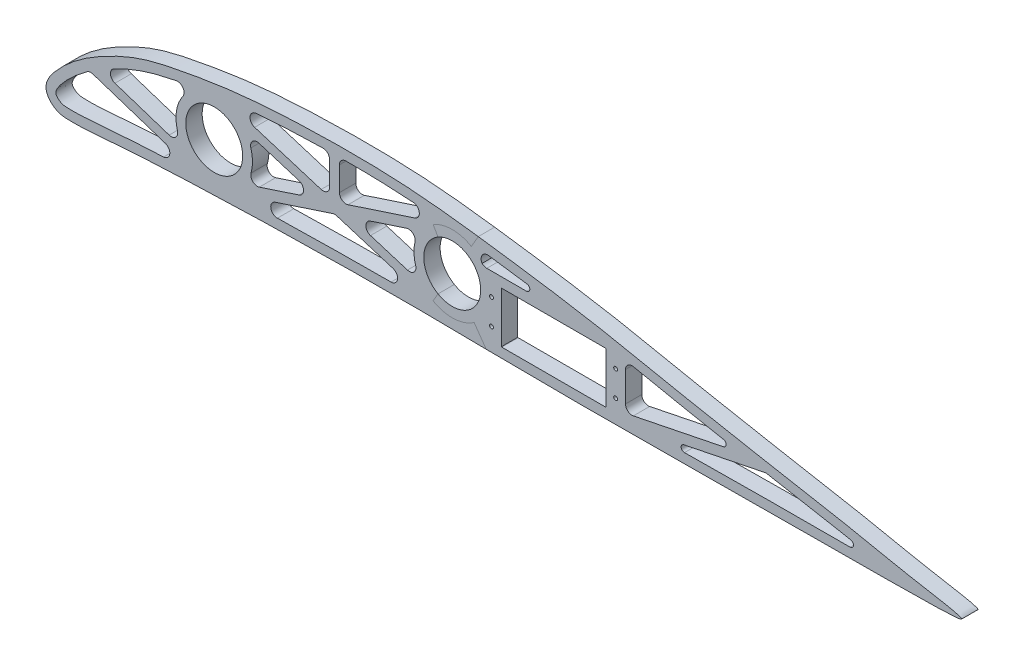
SolidWorks part; units mm, degrees
ref_plane "Front Plane" through (0, 0, 0) normal (0, 0, 1) x (1, 0, 0)
ref_plane "Top Plane" through (0, 0, 0) normal (0, 1, 0) x (1, 0, 0)
ref_plane "Right Plane" through (0, 0, 0) normal (1, 0, 0) x (0, 0, -1)
curve "Curve2"
  spline degree 3 poles (335.2351, -1.0002, 0) (365.8399, -0.7578, 0) (335.068, 4.1779, 0) (315.5959, 8.5123, 0) (283.7557, 14.215, 0) (248.7119, 20.6229, 0) (213.0993, 28.2961, 0) (177.4389, 33.5333, 0) (141.8604, 38.2675, 0) (106.138, 38.4812, 0) (76.3937, 36.9037, 0) (52.7831, 32.9871, 0) (37.7504, 29.8496, 0) (26.1237, 24.7709, 0) (17.1735, 19.9778, 0) (9.6748, 14.5696, 0) (3.4982, 8.4999, 0) (-2.4515, 0.9243, 0) (3.7121, -5.3477, 0) (10.4481, -5.6922, 0) (17.8596, -5.3149, 0) (26.7315, -4.5493, 0) (38.5676, -3.7193, 0) (53.3791, -3.044, 0) (77.0722, -2.1352, 0) (106.6998, -1.4625, 0) (142.26, -1.14, 0) (177.831, -1.7864, 0) (213.3484, -1.8913, 0) (249.0801, -1.7216, 0) (283.9883, -1.2505, 0) (315.6348, -1.3975, 0) (335.2351, -1.0002, 0) (365.8399, -0.7578, 0) (335.068, 4.1779, 0) knots -0.097522 -0.048769 -0.024396 0 0.025026 0.049952 0.099684 0.149416 0.199259 0.248703 0.297849 0.346623 0.395439 0.420071 0.445104 0.458263 0.47205 0.487006 0.495455 0.509299 0.518413 0.524589 0.536779 0.54899 0.561193 0.585585 0.609963 0.658715 0.707463 0.756228 0.804981 0.853734 0.902478 0.951231 0.975604 1 1.025026 1.049952 1.099684 periodic
sketch "Sketch3" plane through (0, 0, 0) normal (0, 0, 1) x (1, 0, 0)
  line L1 (324.6822, 2.6136) -> (325.3535, 2.6233)
  line L2 (325.3535, 2.6233) -> (307.9141, 5.9353)
  spline S0 degree 3 poles (335.2351, -1.0002) (365.8399, -0.7578) (335.068, 4.1779) (315.5959, 8.5123) (283.7557, 14.215) (248.7119, 20.6229) (213.0993, 28.2961) (177.4389, 33.5333) (141.8604, 38.2675) (106.138, 38.4812) (76.3937, 36.9037) (52.7831, 32.9871) (37.7504, 29.8496) (26.1237, 24.7709) (17.1735, 19.9778) (9.6748, 14.5696) (3.4982, 8.4999) (-2.4515, 0.9243) (3.7121, -5.3477) (10.4481, -5.6922) (17.8596, -5.3149) (26.7315, -4.5493) (38.5676, -3.7193) (53.3791, -3.044) (77.0722, -2.1352) (106.6998, -1.4625) (142.26, -1.14) (177.831, -1.7864) (213.3484, -1.8913) (249.0801, -1.7216) (283.9883, -1.2505) (315.6348, -1.3975) (335.2351, -1.0002) (365.8399, -0.7578) (335.068, 4.1779) knots -0.097522 -0.048769 -0.024396 0 0.025026 0.049952 0.099684 0.149416 0.199259 0.248703 0.297849 0.346623 0.395439 0.420071 0.445104 0.458263 0.47205 0.487006 0.495455 0.509299 0.518413 0.524589 0.536779 0.54899 0.561193 0.585585 0.609963 0.658715 0.707463 0.756228 0.804981 0.853734 0.902478 0.951231 0.975604 1 1.025026 1.049952 1.099684 only from (355.6, 0) to (355.6, 0) construction
  spline S3 degree 3 poles (307.9141, 5.9353) (307.0863, 6.0925) (305.4377, 6.4038) (302.0805, 7.0309) (296.1287, 8.128) (287.4713, 9.6948) (277.2294, 11.5453) (267.2024, 13.3828) (257.2748, 15.2495) (244.0596, 17.8287) (227.4526, 21.2972) (207.5658, 25.126) (187.5939, 28.193) (167.4715, 31.0351) (147.4425, 33.4718) (127.4415, 34.5599) (107.2387, 34.4562) (90.4094, 33.8122) (77.0776, 32.6931) (67.1623, 31.4738) (57.2616, 29.8392) (47.317, 27.9873) (39.4207, 26.0026) (33.4304, 23.7904) (28.9582, 21.7979) (24.5546, 19.6052) (20.3228, 17.2265) (16.904, 15.0105) (14.2974, 13.1153) (12.4283, 11.6418) (10.6708, 10.1297) (9.0191, 8.5675) (7.3511, 6.8261) (5.6256, 4.8715) (4.5188, 3.3123) (3.9691, 2.2408) (3.7413, 1.5904) (3.6763, 1.1383) (3.6939, 0.9054) (3.7663, 0.6498) (4.0404, 0.1533) (4.499, -0.3861) (5.086, -0.8863) (5.7247, -1.2682) (6.2758, -1.482) (7.0038, -1.6418) (8.2328, -1.7573) (10.2939, -1.7757) (12.7019, -1.7335) (15.1576, -1.6209) (17.6379, -1.463) (20.9776, -1.2167) (25.1904, -0.8679) (32.0053, -0.347) (40.5143, 0.1734) (50.7079, 0.6434) (60.875, 1.0577) (71.055, 1.4259) (84.63, 1.835) (101.5966, 2.2078) (121.9512, 2.4949) (142.338, 2.5619) (162.7122, 2.3066) (183.0031, 2.0331) (203.2832, 1.9499) (223.6381, 1.9709) (243.9997, 2.078) (260.7266, 2.2598) (274.2438, 2.3928) (284.5572, 2.4608) (295.1146, 2.4761) (303.8218, 2.4778) (310.5638, 2.492) (315.4692, 2.5141) (320.164, 2.5522) (323.1654, 2.5918) (324.6822, 2.6136) knots 0.06655 0.06655 0.06655 0.06655 0.070034 0.073518 0.080485 0.09442 0.108355 0.122289 0.136224 0.150159 0.178028 0.205897 0.233767 0.261636 0.289506 0.317375 0.345244 0.373114 0.387048 0.400983 0.414918 0.428853 0.442787 0.449755 0.456722 0.463689 0.470657 0.477624 0.481108 0.484591 0.488075 0.491559 0.495042 0.498526 0.50201 0.503752 0.505493 0.507235 0.508977 0.510719 0.512461 0.514203 0.515944 0.517686 0.519428 0.52117 0.522912 0.526395 0.529879 0.533363 0.536846 0.54033 0.547298 0.554265 0.5682 0.582134 0.596069 0.610004 0.623938 0.651808 0.679677 0.707547 0.735416 0.763285 0.791155 0.819024 0.846894 0.874763 0.888698 0.902632 0.916567 0.930502 0.937469 0.944436 0.951404 0.958371 0.958371 0.958371 0.958371
  spline S4 degree 3 poles (335.2351, -1.0002) (365.8399, -0.7578) (335.068, 4.1779) (315.5959, 8.5123) (283.7557, 14.215) (248.7119, 20.6229) (213.0993, 28.2961) (177.4389, 33.5333) (141.8604, 38.2675) (106.138, 38.4812) (76.3937, 36.9037) (52.7831, 32.9871) (37.7504, 29.8496) (26.1237, 24.7709) (17.1735, 19.9778) (9.6748, 14.5696) (3.4982, 8.4999) (-2.4515, 0.9243) (3.7121, -5.3477) (10.4481, -5.6922) (17.8596, -5.3149) (26.7315, -4.5493) (38.5676, -3.7193) (53.3791, -3.044) (77.0722, -2.1352) (106.6998, -1.4625) (142.26, -1.14) (177.831, -1.7864) (213.3484, -1.8913) (249.0801, -1.7216) (283.9883, -1.2505) (315.6348, -1.3975) (335.2351, -1.0002) (365.8399, -0.7578) (335.068, 4.1779) knots -0.097522 -0.048769 -0.024396 0 0.025026 0.049952 0.099684 0.149416 0.199259 0.248703 0.297849 0.346623 0.395439 0.420071 0.445104 0.458263 0.47205 0.487006 0.495455 0.509299 0.518413 0.524589 0.536779 0.54899 0.561193 0.585585 0.609963 0.658715 0.707463 0.756228 0.804981 0.853734 0.902478 0.951231 0.975604 1 1.025026 1.049952 1.099684 only from (355.6, 0) to (355.6, 0)
extrude "Outline" add sketch "Sketch3" along normal blind 6.35
curve "Curve3"
  spline degree 3 poles (355.6, 0, 0) (349.661, 1.3249, 0) (337.8068, 3.9693, 0) (314.0213, 8.6322, 0) (284.2903, 14.1743, 0) (248.5683, 20.6338, 0) (213.1375, 28.2932, 0) (177.4288, 33.5341, 0) (141.8629, 38.2672, 0) (106.1377, 38.4813, 0) (76.3924, 36.9036, 0) (52.7856, 32.9873, 0) (37.7426, 29.8491, 0) (26.1384, 24.7718, 0) (17.1124, 19.9739, 0) (9.8782, 14.5828, 0) (2.9933, 8.4673, 0) (1.1467, 3.2437, 0) (0, 0, 0) knots 0 0 0 0 0.049139 0.09808 0.195728 0.293375 0.391241 0.488324 0.584822 0.680589 0.776437 0.824803 0.873954 0.899793 0.926862 0.956228 0.972818 1 1 1 1
curve "Curve4"
  spline degree 3 poles (0, 0, 0) (1.2949, -2.0031, 0) (3.4671, -5.3636, 0) (10.5655, -5.6846, 0) (17.8199, -5.3174, 0) (26.7419, -4.5486, 0) (38.5617, -3.7197, 0) (53.3811, -3.0439, 0) (77.0712, -2.1353, 0) (106.6995, -1.4625, 0) (142.2626, -1.1402, 0) (177.8212, -1.7857, 0) (213.3851, -1.8941, 0) (248.9429, -1.7111, 0) (284.5004, -1.2895, 0) (314.1274, -1.2827, 0) (337.8466, -1.1991, 0) (349.6804, -0.3998, 0) (355.6, 0, 0) knots 0 0 0 0 0.018575 0.03116 0.056003 0.080886 0.105755 0.155463 0.205144 0.304495 0.40384 0.503218 0.602571 0.701924 0.80126 0.900613 0.950284 1 1 1 1
sketch "Sketch4" plane through (0, 0, 6.35) normal (0, 0, 1) x (1, 0, 0)
  line L0 (157.6922, 2.3692) -> (157.6922, 0.8557)
  line L1 (176.7422, 2.1257) -> (217.3822, 2.1257)
  line L2 (176.7422, 2.1257) -> (176.7422, 21.9377)
  line L3 (176.7422, 21.9377) -> (217.3822, 21.9377)
  line L4 (217.3822, 2.1257) -> (217.3822, 21.9377)
  line L5 (165.9635, 0.8557) -> (225.0022, 0.8557)
  line L7 (169.8663, 25.7477) -> (213.3765, 25.7477)
  line L8 (225.0022, 0.8557) -> (225.0022, 22.8309)
  line L9 (157.6922, 0.8557) -> (165.9635, 0.8557)
  line L12 (213.3765, 25.7477) -> (225.0022, 22.8309)
  circle A0 centre (65.2362, 16.0821) radius 11.049
  circle A1 centre (65.2362, 16.0821) radius 14.859
  circle A2 centre (157.6922, 17.2282) radius 11.049
  arc A3 (169.8663, 25.7477) -> (157.6922, 2.3692) centre (157.6922, 17.2282) ccw
  spline S0 degree 3 poles (-1038.5734, -1708.4775) (56.5957, 197.5041) (-23.9133, -4.1254) (10.5655, -5.6846) (17.8199, -5.3174) (26.7419, -4.5486) (38.5617, -3.7197) (53.3811, -3.0439) (77.0712, -2.1353) (106.6995, -1.4625) (142.2626, -1.1402) (177.8212, -1.7857) (213.3851, -1.8941) (248.9429, -1.7111) (284.5004, -1.2895) (314.1274, -1.2827) (467.1025, -0.7435) (604.2683, 106.9608) (814.6729, -1933.1464) knots -0.216018 -0.216018 -0.216018 -0.216018 0.018575 0.03116 0.056003 0.080886 0.105755 0.155463 0.205144 0.304495 0.40384 0.503218 0.602571 0.701924 0.80126 0.900613 0.950284 2.083015 2.083015 2.083015 2.083015 only from (0, 0) to (355.6, 0) construction
  spline S1 degree 3 poles (0, 0) (1.2949, -2.0031) (3.4671, -5.3636) (10.5655, -5.6846) (17.8199, -5.3174) (26.7419, -4.5486) (38.5617, -3.7197) (53.3811, -3.0439) (77.0712, -2.1353) (106.6995, -1.4625) (142.2626, -1.1402) (177.8212, -1.7857) (213.3851, -1.8941) (248.9429, -1.7111) (284.5004, -1.2895) (314.1274, -1.2827) (337.8466, -1.1991) (349.6804, -0.3998) (355.6, 0) knots 0 0 0 0 0.018575 0.03116 0.056003 0.080886 0.105755 0.155463 0.205144 0.304495 0.40384 0.503218 0.602571 0.701924 0.80126 0.900613 0.950284 1 1 1 1 construction
  spline S2 degree 3 poles (1264.4447, 1754.3849) (679.5845, -139.9452) (510.5114, -29.8876) (314.0213, 8.6322) (284.2903, 14.1743) (248.5683, 20.6338) (213.1375, 28.2932) (177.4288, 33.5341) (141.8629, 38.2672) (106.1377, 38.4813) (76.3924, 36.9036) (52.7856, 32.9873) (37.7426, 29.8491) (26.1384, 24.7718) (17.1124, 19.9739) (9.8782, 14.5828) (-28.7294, -19.7107) (107.4887, -169.8565) (-1713.5684, 1028.2618) knots -1.421165 -1.421165 -1.421165 -1.421165 0.049139 0.09808 0.195728 0.293375 0.391241 0.488324 0.584822 0.680589 0.776437 0.824803 0.873954 0.899793 0.926862 0.956228 0.972818 1.336994 1.336994 1.336994 1.336994 only from (355.6, 0) to (0, 0) construction
  spline S3 degree 3 poles (355.6, 0) (349.661, 1.3249) (337.8068, 3.9693) (314.0213, 8.6322) (284.2903, 14.1743) (248.5683, 20.6338) (213.1375, 28.2932) (177.4288, 33.5341) (141.8629, 38.2672) (106.1377, 38.4813) (76.3924, 36.9036) (52.7856, 32.9873) (37.7426, 29.8491) (26.1384, 24.7718) (17.1124, 19.9739) (9.8782, 14.5828) (2.9933, 8.4673) (1.1467, 3.2437) (0, 0) knots 0 0 0 0 0.049139 0.09808 0.195728 0.293375 0.391241 0.488324 0.584822 0.680589 0.776437 0.824803 0.873954 0.899793 0.926862 0.956228 0.972818 1 1 1 1 construction
  spline S4 degree 1 poles (3.1997, 2.0683) (355.3433, 3.8013) knots 0 0 1 1 construction
  spline S5 degree 3 poles (3.1997, 2.0683) (3.3321, 1.8636) (3.6027, 1.445) (4.1055, 0.6857) (4.9359, -0.4817) (5.6225, -1.1441) (6.009, -1.3731) (6.2112, -1.4673) (6.7384, -1.6184) (7.7394, -1.7276) (9.0432, -1.7604) (10.4239, -1.7667) (12.2132, -1.743) (14.4421, -1.6605) (17.1268, -1.4991) (19.8677, -1.2997) (22.6408, -1.0794) (26.3762, -0.7752) (31.0669, -0.4219) (36.6781, -0.0599) (44.1669, 0.3502) (52.9307, 0.7361) (61.6818, 1.0858) (69.1483, 1.3554) (77.1939, 1.6165) (90.8411, 1.9875) (109.5082, 2.3415) (131.3685, 2.5726) (148.9932, 2.4807) (160.7191, 2.3302) (167.1321, 2.2447) (173.5416, 2.1604) (184.1772, 2.0407) (200.6606, 1.9512) (221.4021, 1.963) (243.7529, 2.0787) (266.1087, 2.3057) (284.771, 2.4686) (299.6966, 2.5154) (310.8807, 2.5367) (322.0754, 2.554) (333.2026, 2.6081) (344.2003, 3.0428) (351.6389, 3.5511) (355.3433, 3.8013) knots 0 0 0 0 0.001953 0.003906 0.007812 0.015625 0.017578 0.019531 0.023438 0.027344 0.03125 0.035156 0.039062 0.046875 0.054688 0.0625 0.070312 0.078125 0.09375 0.109375 0.125 0.15625 0.182674 0.198299 0.21875 0.25 0.3125 0.375 0.432885 0.459761 0.473199 0.486637 0.513513 0.5625 0.625 0.6875 0.75 0.8125 0.84375 0.875 0.90625 0.9375 0.96875 1 1 1 1 construction
  spline S6 degree 1 poles (354.7705, -3.7186) (3.5921, -1.2699) knots 0 0 1 1 construction
  spline S7 degree 3 poles (354.7705, -3.7186) (351.0001, -2.8775) (343.4484, -1.1902) (332.1602, 1.1916) (320.7975, 3.4152) (305.6082, 6.3199) (286.6083, 9.8584) (267.5698, 13.3173) (252.3238, 16.2026) (237.0891, 19.2527) (221.963, 22.4102) (206.8512, 25.1592) (195.4518, 26.9969) (184.0073, 28.6859) (172.9363, 30.2438) (163.8033, 31.4643) (156.1725, 32.3779) (148.1302, 33.2277) (138.2018, 34.0056) (122.9231, 34.5796) (107.5251, 34.4411) (92.1596, 33.8524) (80.706, 33.056) (71.4478, 32.0334) (65.0502, 31.1011) (61.2777, 30.4982) (57.3046, 29.8218) (52.369, 28.92) (46.7644, 27.8016) (41.3075, 26.4731) (36.0723, 24.835) (30.9745, 22.7404) (25.8637, 20.296) (20.973, 17.6478) (16.3954, 14.6739) (12.7284, 11.8586) (9.8342, 9.4451) (8.0099, 7.7006) (6.7041, 6.0111) (5.5686, 3.911) (4.7283, 1.8735) (4.0826, 0.1172) (3.7542, -0.8114) (3.5921, -1.2699) knots 0 0 0 0 0.03125 0.0625 0.09375 0.125 0.1875 0.25 0.28125 0.3125 0.375 0.40625 0.4375 0.46875 0.5 0.527813 0.543438 0.5625 0.59375 0.625 0.6875 0.71875 0.75 0.78125 0.795217 0.803029 0.8125 0.828125 0.84375 0.859375 0.875 0.890625 0.90625 0.921875 0.9375 0.953125 0.960938 0.96875 0.976562 0.984375 0.992188 0.996094 1 1 1 1 construction
  dimension "D3" = 22.098
  dimension "D4" = 3.81
  dimension "D5" = 22.098
  dimension "D6" = 3.81
  dimension "D7" = 40.64
  dimension "D8" = 19.812
  dimension "D9" = 1.27
  dimension "D10" = 3.81
  dimension "D11" = 7.62
  dimension "D12" = 19.05
  dimension "D1" = 3.81
  dimension "D2" = 3.81
extrude "Spar and Servo" add sketch "Sketch4" against normal up to surface (6.35 mm away)
sketch "Sketch5" plane through (0, 0, 6.35) normal (0, 0, 1) x (1, 0, 0)
  line L0 (158.7526, 33.8049) -> (113.8719, 19.0824)
  line L1 (158.7526, 33.8049) -> (159.9401, 30.1847)
  line L3 (159.9401, 30.1847) -> (118.3178, 16.5311)
  line L4 (64.6737, 29.1211) -> (105.7641, 16.4228)
  line L5 (64.6737, 29.1211) -> (65.7987, 32.7612) construction
  line L6 (65.2362, 16.0821) -> (65.2362, 1.2231) construction
  line L7 (157.1298, 0.5491) -> (158.2547, 4.1892) construction
  line L8 (65.7987, 32.7612) -> (110.0619, 19.0824)
  line L9 (65.2362, 16.0821) -> (65.2362, 30.9411) construction
  line L10 (157.6922, 17.2282) -> (157.6922, 2.3692) construction
  line L11 (64.6737, 29.1211) -> (63.0659, 30.5361)
  line L12 (63.0659, 30.5361) -> (62.9457, 32.4209)
  line L13 (62.9457, 32.4209) -> (65.7987, 32.7612)
  line L14 (105.7641, 16.4228) -> (65.2362, 3.1281)
  line L15 (112.0582, 14.4777) -> (157.1298, 0.5491)
  line L16 (118.3178, 16.5311) -> (158.2547, 4.1892)
  line L17 (112.0582, 14.4777) -> (65.2362, -0.8816)
  line L18 (110.0619, 19.0824) -> (110.0619, 36.8624)
  line L19 (110.0619, 36.8624) -> (113.8719, 36.8624)
  line L20 (113.8719, 36.8624) -> (113.8719, 19.0824)
  line L21 (65.2362, 3.1281) -> (18.7364, 18.3818)
  line L22 (18.7364, 18.3818) -> (14.7118, 15.6922)
  line L23 (14.7118, 15.6922) -> (65.2362, -0.8816)
  line L24 (224.6232, 3.8567) -> (274.7988, 14.0446)
  line L25 (224.6232, 3.8567) -> (225.3813, 0.1228)
  line L26 (274.7988, 14.0446) -> (275.557, 10.3108) construction
  line L27 (225.3813, 0.1228) -> (275.557, 10.3108)
  line L28 (224.6232, 3.8567) -> (275.557, 10.3108) construction
  line L29 (274.7988, 14.0446) -> (225.3813, 0.1228) construction
  line L31 (225.0022, 21.7322) -> (325.3535, 2.6233) construction
  line L32 (275.557, 10.3108) -> (281.78, 11.5744)
  line L33 (281.78, 11.5744) -> (274.7988, 14.0446)
  line L34 (325.3535, 2.6233) -> (225.0022, 1.9898) construction
  line L35 (312.5641, 5.0586) -> (313.255, 7.5294)
  line L36 (313.255, 7.5294) -> (334.4122, 2.0171)
  line L37 (334.4122, 2.0171) -> (314.2414, 0.15)
  line L38 (314.2414, 0.15) -> (312.3345, 2.5411)
  line L39 (158.2547, 4.1892) -> (160.9316, 1.2231)
  line L40 (160.9316, 1.2231) -> (157.1298, 0.5491)
  circle A0 centre (65.2362, 16.0821) radius 14.859 construction
  arc A1 (62.6472, 30.7138) -> (63.1227, 30.79) centre (65.2362, 16.0821) ccw construction
  circle A2 centre (157.6922, 17.2282) radius 14.859 construction
  arc A3 (159.3463, 31.9948) -> (157.6922, 2.3692) centre (157.6922, 17.2282) ccw construction
  arc A4 (312.5641, 5.0586) -> (312.3345, 2.5411) centre (312.3265, 3.8111) cw
  point P0 (159.3463, 31.9948)
  point P5 (225.0022, 1.9898)
  point P14 (65.2362, 30.9411)
  point P19 (250.0901, 7.0837)
  point P28 (157.6922, 2.3692)
  point P47 (275.1779, 12.1777)
  point P48 (275.1779, 12.1777)
  dimension "D9" = 1.27
  dimension "D1" = 3.81
  dimension "D2" = 3.81
  dimension "D3" = 3.81
  dimension "D4" = 17.78
  dimension "D5" = 3.81
  dimension "D6" = 1.905
  dimension "D7" = 3.81
  dimension "D8" = 6.35
extrude "Supports" add sketch "Sketch5" against normal up to surface (6.35 mm away) up to face at (120.3359, 25.5571, 0)
fillet "0.10 Fillets" radius 2.54 25 edges at (279.5666, 11.125, 3.175) (225.0022, 3.9336, 3.175) (225.0022, 21.7322, 3.175) (118.3178, 16.5311, 3.175) (146.0862, 7.9497, 3.175) (145.2623, 25.3699, 3.175) (154.819, 32.5145, 3.175) (113.8719, 34.4495, 3.175) (113.8719, 19.0824, 3.175) (112.0582, 14.4777, 3.175) (110.0619, 34.3992, 3.175) (110.0619, 19.0824, 3.175) (105.7641, 16.4228, 3.175) (76.9819, 6.9812, 3.175) (69.2475, 31.6954, 3.175) (76.8422, 25.3606, 3.175) (21.0735, 17.6151, 3.175) (53.4905, 6.9812, 3.175) (151.0016, 2.4429, 3.175) (72.3709, 1.4588, 3.175) (59.5094, 0.997, 3.175) (16.9074, 14.972, 3.175) (169.8663, 25.7477, 3.175)
fillet "0.05 Fillets" radius 1.27 3 edges at (234.7938, 2.034, 3.175) (269.4915, 12.967, 3.175) (203.1185, 25.7477, 3.175)
sketch "Sketch6" plane through (0, 0, 6.35) normal (0, 0, 1) x (1, 0, 0)
  line L0 (176.7422, 21.9377) -> (217.3822, 2.1257) construction
  line L1 (176.9334, 2.1257) -> (217.3822, 21.9377) construction
  circle A0 centre (172.9322, 16.9974) radius 0.762
  circle A2 centre (221.1922, 16.9974) radius 0.762
  circle A3 centre (221.1922, 7.066) radius 0.762
  circle A4 centre (172.9322, 7.066) radius 0.762
  point P16 (197.0622, 12.0317)
  dimension "D1" = 1.524
  dimension "D4" = 24.13
  dimension "D5" = 4.9657
  dimension "D6" = 9.9314
  dimension "D7" = 48.26
  dimension "D2" = 2
  dimension "D3" = 2
extrude "Cut-Extrude1" cut sketch "Sketch6" against normal through all both and the other way through all
sketch "Sketch7" plane through (0, 0, 0) normal (0, 0, 1) x (1, 0, 0)
  line L0 (152.1677, 26.7969) -> (150.2627, 30.0964)
  line L1 (157.6922, 28.2772) -> (157.6922, 17.2282) construction
  line L2 (152.1677, 26.7969) -> (157.6922, 17.2282) construction
  line L3 (166.215, 5.0564) -> (170.886, -1.6144)
  line L4 (157.6922, 17.2282) -> (164.0297, 8.1774) construction
  line L5 (165.1217, 30.0964) -> (168.2373, 35.4928)
  line L6 (150.2627, 4.3599) -> (157.6922, 17.2282) construction
  line L7 (152.1677, 7.6595) -> (150.2627, 4.3599)
  arc A2 (164.0297, 8.1774) -> (152.1677, 26.7969) centre (157.6922, 17.2282) ccw
  arc A3 (150.2627, 4.3599) -> (166.215, 5.0564) centre (157.6922, 17.2282) ccw
  arc A5 (165.1217, 30.0964) -> (150.2627, 30.0964) centre (157.6922, 17.2282) ccw
  arc A6 (164.0297, 8.1774) -> (152.1677, 7.6595) centre (157.6922, 17.2282) cw
  dimension "D5" = 3.81
  dimension "D1" = 30
  dimension "D2" = 145
  dimension "D3" = 30
  dimension "D4" = 150
split "Split2" trim tools "Sketch7" bodies to split 104 resulting bodies 107 108
